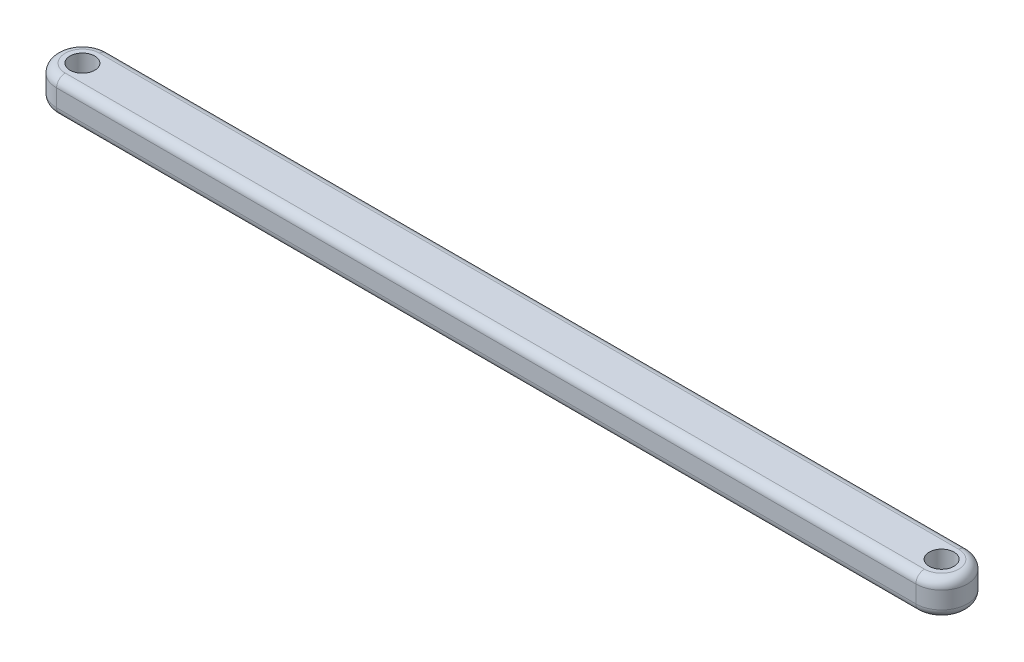
SolidWorks part; units mm, degrees
ref_plane "Front Plane" through (0, 0, 0) normal (0, 0, 1) x (1, 0, 0)
ref_plane "Top Plane" through (0, 0, 0) normal (0, 1, 0) x (1, 0, 0)
ref_plane "Right Plane" through (0, 0, 0) normal (1, 0, 0) x (0, 0, -1)
sketch "Sketch1" plane through (0, 0, 0) normal (0, 1, 0) x (1, 0, 0)
  line L0 (0, 0) -> (158.75, 0) construction
  line L1 (0, 4.7625) -> (158.75, 4.7625)
  line L2 (0, -4.7625) -> (158.75, -4.7625)
  arc A0 (0, 4.7625) -> (0, -4.7625) centre (0, 0) ccw
  arc A1 (158.75, -4.7625) -> (158.75, 4.7625) centre (158.75, 0) ccw
  point P3 (79.375, 0)
  dimension "D1" = 158.75
  dimension "D2" = 9.525
extrude "Boss-Extrude1" add sketch "Sketch1" along normal mid plane 6.35
sketch "Sketch2" plane through (0, 3.175, 0) normal (0, 1, 0) x (1, 0, 0)
  circle A0 centre (0, 0) radius 2.286
  circle A1 centre (158.75, 0) radius 2.286
  dimension "D1" = 4.572
extrude "Cut-Extrude1" cut sketch "Sketch2" against normal through all
fillet "Fillet1" radius 1.5875 8 edges at (163.5125, -3.175, 0) (79.375, -3.175, 4.7625) (-4.7625, -3.175, 0) (163.5125, 3.175, 0) (79.375, 3.175, 4.7625) (-4.7625, 3.175, 0) (79.375, -3.175, -4.7625) (79.375, 3.175, -4.7625)
